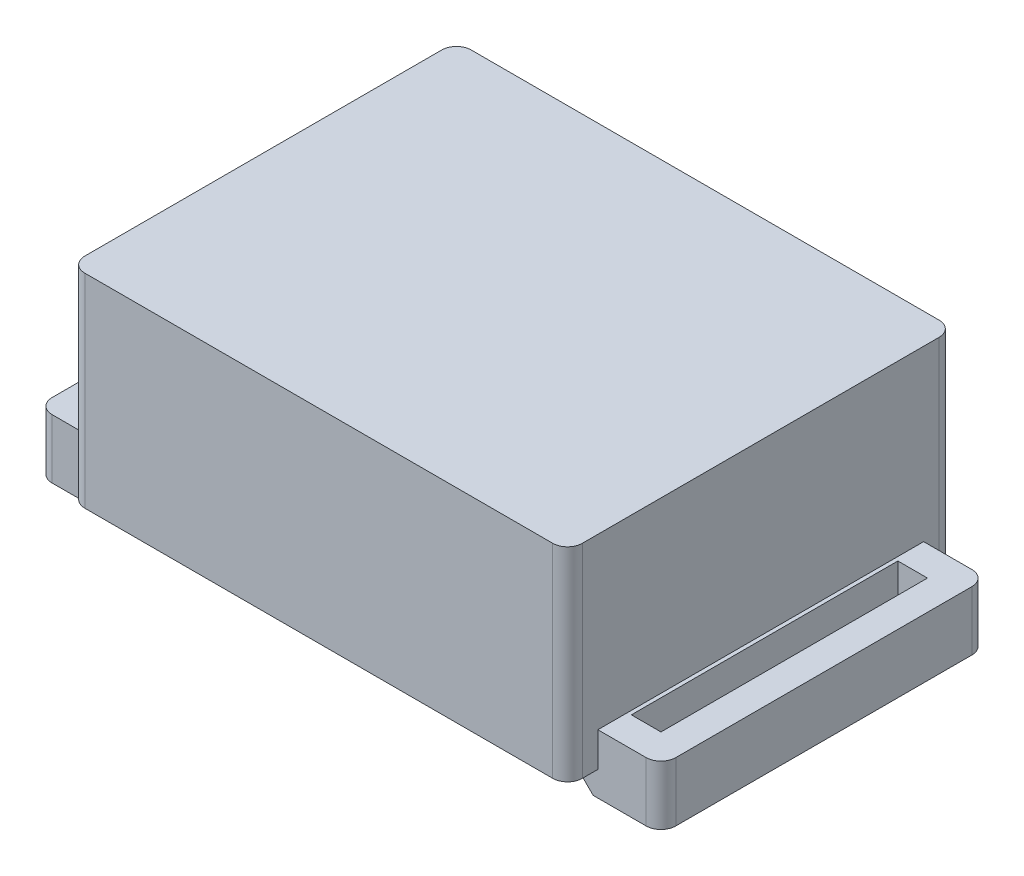
SolidWorks part; units mm, degrees
ref_plane "Front Plane" through (0, 0, 0) normal (0, 0, 1) x (1, 0, 0)
ref_plane "Top Plane" through (0, 0, 0) normal (0, 1, 0) x (1, 0, 0)
ref_plane "Right Plane" through (0, 0, 0) normal (1, 0, 0) x (0, 0, -1)
sketch "Sketch1" plane through (0, 0, 0) normal (0, 1, 0) x (1, 0, 0)
  line L1 (16.8, -13.05) -> (-16.8, -13.05)
  line L2 (16.8, -13.05) -> (16.8, 13.05)
  line L3 (16.8, 13.05) -> (-16.8, 13.05)
  line L4 (-16.8, -13.05) -> (-16.8, 13.05)
  line L5 (16.8, -13.05) -> (-16.8, 13.05) construction
  line L6 (16.8, 13.05) -> (-16.8, -13.05) construction
  point P0 (0, 0)
  dimension "D1" = 33.6
  dimension "D2" = 26.1
extrude "Boss-Extrude1" add sketch "Sketch1" along normal blind 13.75
sketch "Sketch2" plane through (0, 0, 0) normal (0, 1, 0) x (1, 0, 0)
  line L0 (16.8, -13.05) -> (16.8, 13.05) construction
  line L1 (21.06, -11) -> (16.8, -11)
  line L2 (21.06, -11) -> (21.06, 11)
  line L3 (21.06, 11) -> (16.8, 11)
  line L4 (16.8, -11) -> (16.8, 11)
  line L5 (21.06, -11) -> (16.8, 11) construction
  line L6 (21.06, 11) -> (16.8, -11) construction
  line L7 (-21.06, -11) -> (-16.8, -11)
  line L8 (-21.06, -11) -> (-21.06, 11)
  line L9 (-21.06, 11) -> (-16.8, 11)
  line L10 (-16.8, -11) -> (-16.8, 11)
  line L11 (-21.06, -11) -> (-16.8, 11) construction
  line L12 (-21.06, 11) -> (-16.8, -11) construction
  line L13 (-16.8, 13.05) -> (-16.8, -13.05) construction
  point P0 (18.93, 0)
  point P5 (-18.93, 0)
  point P10 (0, 0)
  point P12 (0, 0)
  dimension "D1" = 22
  dimension "D2" = 4.26
extrude "Boss-Extrude2" add sketch "Sketch2" against normal blind 1.68 and the other way blind 2.32
sketch "Sketch3" plane through (0, 2.32, 0) normal (0, 1, 0) x (1, 0, 0)
  line L0 (21.06, 11) -> (16.8, 11) construction
  line L13 (0, -1000) -> (0, 49000) construction
  line L18 (-17.06, -9) -> (-19.06, 9) construction
  line L19 (17.06, 9) -> (19.06, 9)
  line L20 (17.06, 9) -> (17.06, -9)
  line L21 (17.06, -9) -> (19.06, -9)
  line L22 (19.06, 9) -> (19.06, -9)
  line L23 (17.06, 9) -> (19.06, -9) construction
  line L24 (17.06, -9) -> (19.06, 9) construction
  line L25 (16.8, -11) -> (21.06, -11) construction
  line L26 (21.06, -11) -> (21.06, 11) construction
  line L27 (-17.06, 9) -> (-19.06, -9) construction
  line L28 (-19.06, 9) -> (-19.06, -9)
  line L29 (-17.06, -9) -> (-19.06, -9)
  line L30 (-17.06, 9) -> (-17.06, -9)
  line L31 (-17.06, 9) -> (-19.06, 9)
  point P5 (18.06, 0)
  point P21 (-18.06, 0)
  dimension "D1" = 2
  dimension "D2" = 2
  dimension "D3" = 2
  dimension "D4" = 2
extrude "Cut-Extrude1" cut sketch "Sketch3" against normal through all
chamfer "Chamfer1" distance 2 angle 45 2 edges at (16.8, 0, 0) (-16.8, 0, 0)
fillet "Fillet1" radius 1 8 edges at (16.8, 6.875, 13.05) (16.8, 6.875, -13.05) (-16.8, 6.875, -13.05) (-16.8, 6.875, 13.05) (-21.06, 0.32, 11) (-21.06, 0.32, -11) (21.06, 0.32, -11) (21.06, 0.32, 11)
